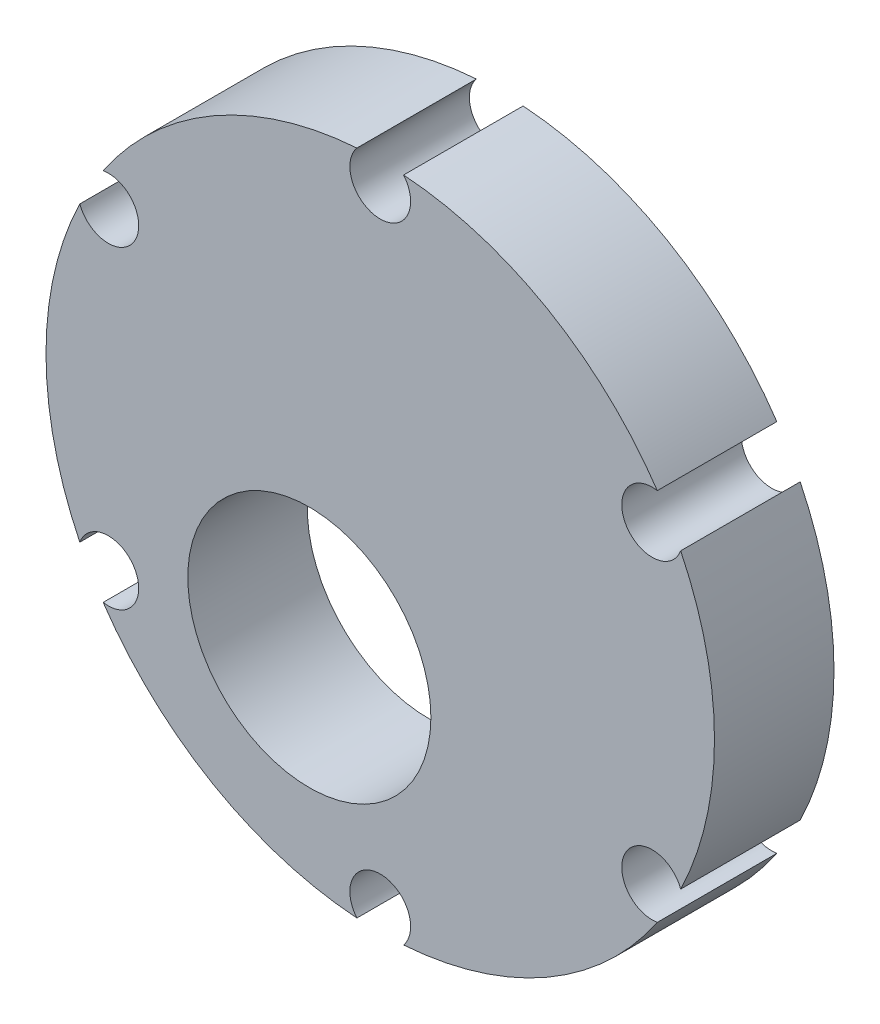
SolidWorks part; units mm, degrees
ref_plane "Front Plane" through (0, 0, 0) normal (0, 0, 1) x (1, 0, 0)
ref_plane "Top Plane" through (0, 0, 0) normal (0, 1, 0) x (1, 0, 0)
ref_plane "Right Plane" through (0, 0, 0) normal (1, 0, 0) x (0, 0, -1)
sketch "Sketch1" plane through (0, 0, 0) normal (0, 0, 1) x (1, 0, 0)
  circle A0 centre (0, 0) radius 16.5
  dimension "D1" = 33
extrude "Boss-Extrude1" add sketch "Sketch1" along normal blind 5.9
sketch "Sketch2" plane through (0, 0, 5.9) normal (0, 0, 1) x (1, 0, 0)
  circle A0 centre (0, 15.5) radius 1.5
  circle A1 centre (13.4234, 7.75) radius 1.5
  circle A2 centre (13.4234, -7.75) radius 1.5
  circle A3 centre (0, -15.5) radius 1.5
  circle A4 centre (-13.4234, -7.75) radius 1.5
  circle A5 centre (-13.4234, 7.75) radius 1.5
  point P15 (0, 0)
  dimension "D1" = 3
  dimension "D2" = 15.5
  dimension "D3" = 6
extrude "Cut-Extrude1" cut sketch "Sketch2" against normal through all
sketch "Sketch3" plane through (0, 0, 5.9) normal (0, 0, 1) x (1, 0, 0)
  line L0 (-3.5, -6.0622) -> (0, 0) construction
  line L1 (0, 0) -> (0, -15.5) construction
  circle A0 centre (-3.5, -6.0622) radius 6
  dimension "D1" = 12
  dimension "D2" = 30
  dimension "D3" = 7
extrude "Cut-Extrude2" cut sketch "Sketch3" against normal through all
equation "\"smallPulleyTeeth\"= 15"
equation "\"largePulleyTeeth\"= 40"
equation "\"eighthThick\"= 2.9mm"
equation "\"sixteenthThick\"= 1.7mm"
equation "\"wheelEighthThick\"=3.0mm"
equation "\"quarterThick\"=5.9mm"
equation "\"OD\"= 145mm"
equation "\"puckAngle\"= 60.5deg"
equation "\"puckDiam\"= 76.5mm"
equation "\"axlePress\"= 5.9mm"
equation "\"D1@Boss-Extrude1\"=\"quarterThick\""
